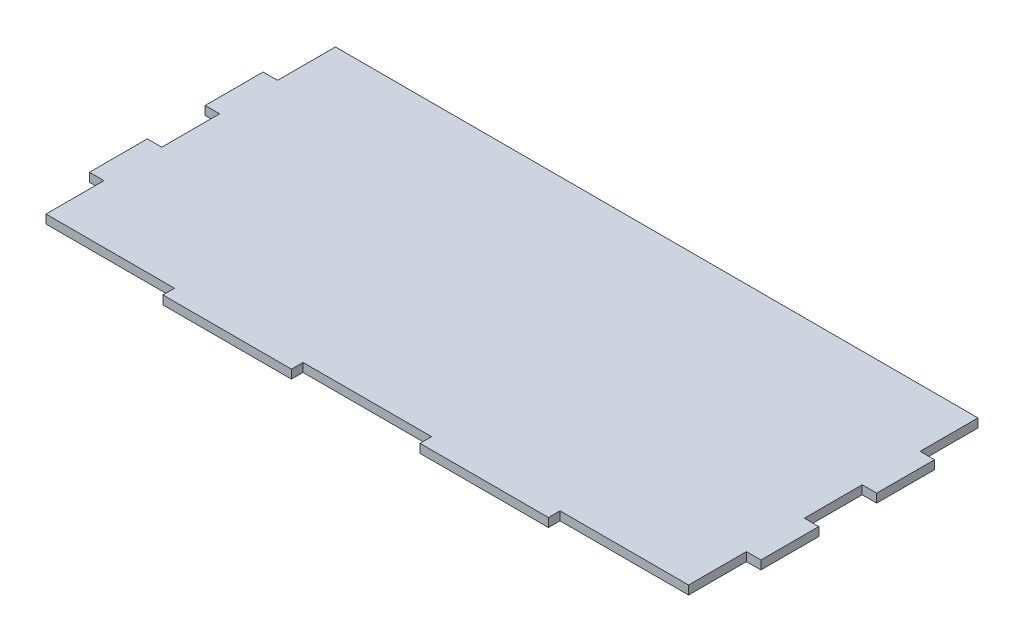
SolidWorks part; units mm, degrees
ref_plane "Front Plane" through (0, 0, 0) normal (0, 0, 1) x (1, 0, 0)
ref_plane "Top Plane" through (0, 0, 0) normal (0, 1, 0) x (1, 0, 0)
ref_plane "Right Plane" through (0, 0, 0) normal (1, 0, 0) x (0, 0, -1)
sketch "Sketch1" plane through (0, 0, 0) normal (0, 1, 0) x (1, 0, 0)
  line L0 (-111, 30) -> (-116, 30)
  line L1 (-111, -50) -> (-66.6, -50)
  line L2 (-111, -50) -> (-111, -30)
  line L3 (-111, 50) -> (111, 50)
  line L4 (111, -50) -> (111, -30)
  line L5 (-111, -50) -> (111, 50) construction
  line L6 (-111, 50) -> (111, -50) construction
  line L7 (-116, 30) -> (-116, 10)
  line L8 (-116, 10) -> (-111, 10)
  line L9 (0, 50) -> (0, -50) construction
  line L10 (-111, -10) -> (-116, -10)
  line L11 (-116, -10) -> (-116, -30)
  line L12 (-116, -30) -> (-111, -30)
  line L13 (-111, 30) -> (-111, 50)
  line L14 (-111, -10) -> (-111, 10)
  line L15 (116, -30) -> (111, -30)
  line L16 (116, -10) -> (116, -30)
  line L17 (111, -10) -> (116, -10)
  line L18 (116, 10) -> (111, 10)
  line L19 (116, 30) -> (116, 10)
  line L20 (111, 30) -> (116, 30)
  line L21 (111, 30) -> (111, 50)
  line L22 (111, -10) -> (111, 10)
  line L23 (-22.2, -50) -> (22.2, -50)
  line L24 (-66.6, -54) -> (-22.2, -54)
  line L25 (-66.6, -54) -> (-66.6, -50)
  line L27 (-22.2, -54) -> (-22.2, -50)
  line L28 (22.2, -54) -> (22.2, -50)
  line L29 (66.6, -54) -> (66.6, -50)
  line L30 (22.2, -54) -> (66.6, -54)
  line L31 (66.6, -50) -> (111, -50)
  point P0 (0, 0)
  dimension "D1" = 222
  dimension "D2" = 100
  dimension "D3" = 20
  dimension "D4" = 20
  dimension "D5" = 5
  dimension "D7" = 44.4
  dimension "D8" = 2
  dimension "D9" = 44.4
  dimension "D10" = 4
  dimension "D6" = 2
extrude "Boss-Extrude1" add sketch "Sketch1" along normal blind 3
